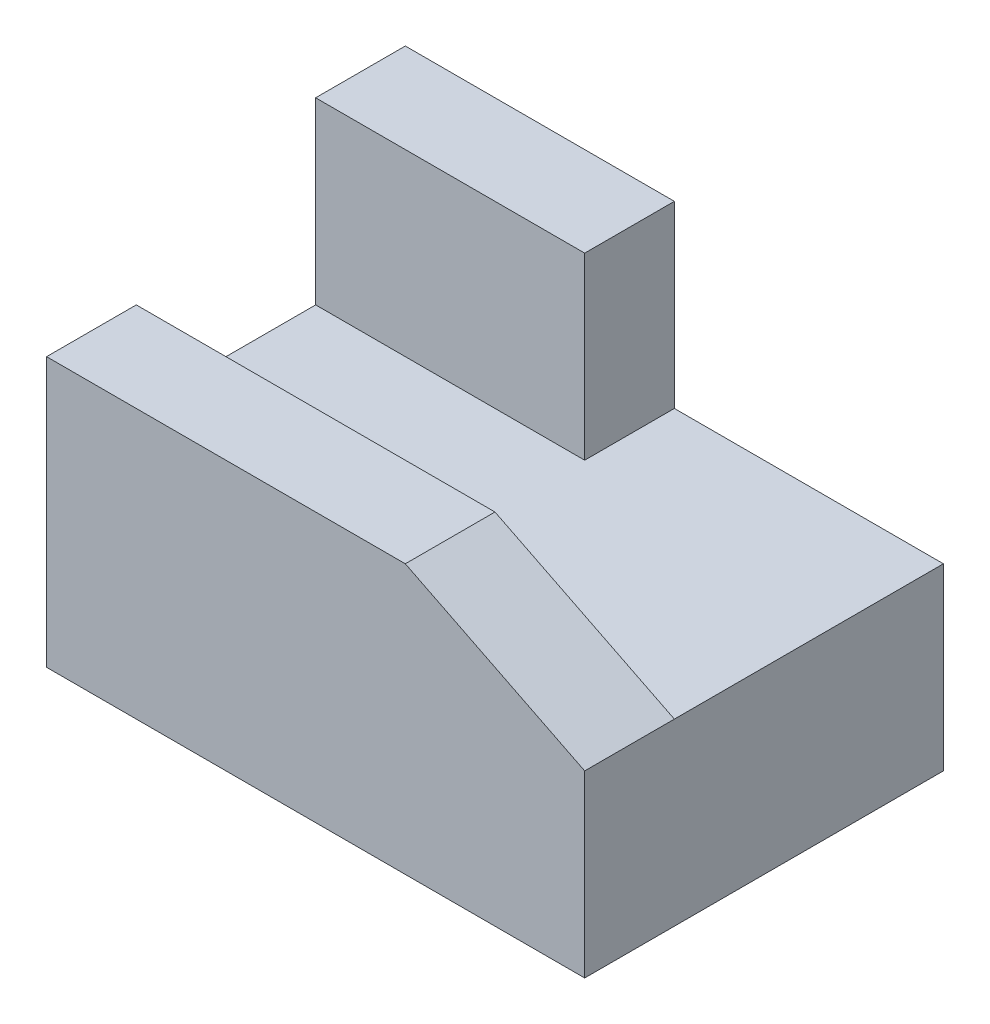
SolidWorks part; units mm, degrees
ref_plane "前基準面" through (0, 0, 0) normal (0, 0, 1) x (1, 0, 0)
ref_plane "上基準面" through (0, 0, 0) normal (0, 1, 0) x (1, 0, 0)
ref_plane "右基準面" through (0, 0, 0) normal (1, 0, 0) x (0, 0, -1)
sketch "草圖1" plane through (0, 0, 0) normal (0, 1, 0) x (1, 0, 0)
  line L1 (15, 10) -> (-15, 10)
  line L2 (15, 10) -> (15, -10)
  line L3 (15, -10) -> (-15, -10)
  line L4 (-15, 10) -> (-15, -10)
  line L5 (15, 10) -> (-15, -10) construction
  line L6 (15, -10) -> (-15, 10) construction
  line L7 (-15, 10) -> (0, 10)
  line L8 (-15, 10) -> (-15, 5)
  line L9 (-15, 5) -> (0, 5)
  line L10 (0, 10) -> (0, 5)
  line L11 (-15, -10) -> (15, -10)
  line L12 (-15, -10) -> (-15, -5)
  line L13 (-15, -5) -> (15, -5)
  line L14 (15, -10) -> (15, -5)
  line L15 (15, -5) -> (5, -5)
  line L16 (15, -5) -> (15, -10)
  line L17 (15, -10) -> (5, -10)
  line L18 (5, -5) -> (5, -10)
  point P0 (0, 0)
  dimension "D1" = 20
  dimension "D2" = 30
  dimension "D3" = 5
  dimension "D4" = 15
  dimension "D5" = 5
  dimension "D6" = 10
extrude "填料-伸長1" add sketch "草圖1" along normal blind 10 contours L10 L1 L4 L9 | L4 L13 L2 L1 L10 L9 | L18 L13 L4 L11 | L13 L18 L3 L2 region at (1.5, 0, -1.5) region at (-7.5, 0, -7.5) region at (10, 0, 7.5) region at (-5, 0, 7.5)
extrude "填料-伸長2" add sketch "草圖1<3>" along normal blind 15 contours L18 L13 L4 L11 | L13 L18 L3 L2 region at (10, 0, 7.5) region at (-5, 0, 7.5)
sketch "草圖1<3>" plane through (0, 0, 0) normal (0, 1, 0) x (1, 0, 0) same geometry as "草圖1"
extrude "填料-伸長3" add sketch "草圖1<4>" along normal blind 20 contours L10 L1 L4 L9 region at (-7.5, 0, -7.5)
sketch "草圖1<4>" plane through (0, 0, 0) normal (0, 1, 0) x (1, 0, 0) same geometry as "草圖1"
sketch "草圖2" plane through (0, 0, 10) normal (0, 0, 1) x (1, 0, 0)
  line L0 (5, 15) -> (15, 10)
  line L1 (15, 15) -> (-15, 15) construction
  line L2 (15, 10) -> (15, 15)
  line L3 (15, 15) -> (5, 15)
  point P5 (7.6287, 15)
  dimension "D1" = 10
extrude "除料-伸長1" cut sketch "草圖2" against normal blind 20
